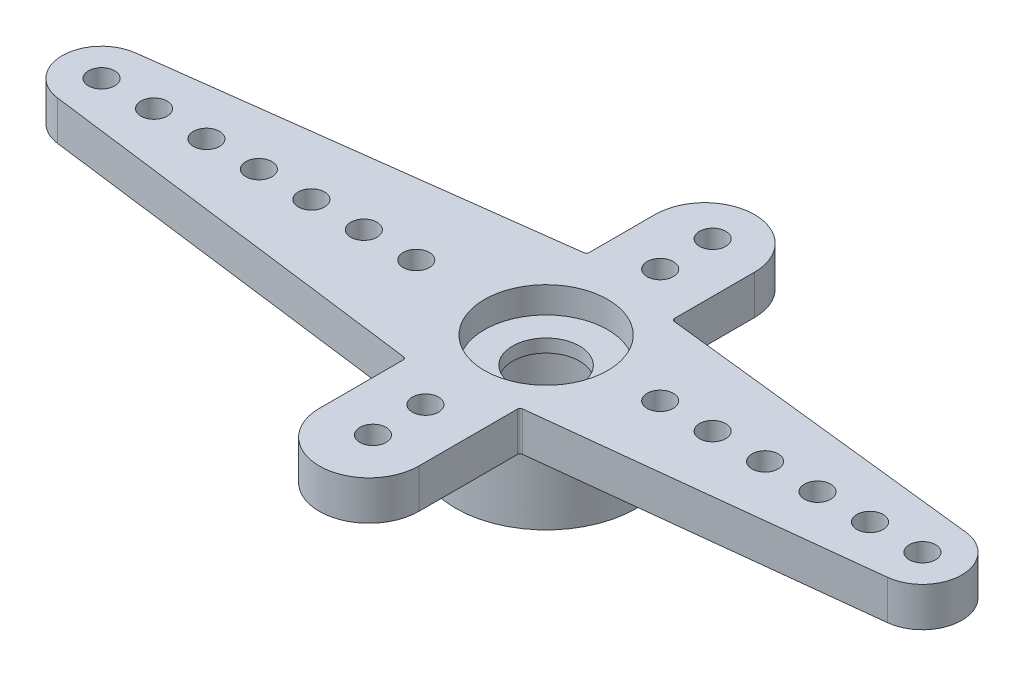
SolidWorks part; units mm, degrees
ref_plane "Ön Düzlem" through (0, 0, 0) normal (0, 0, 1) x (1, 0, 0)
ref_plane "Üst Düzlem" through (0, 0, 0) normal (0, 1, 0) x (1, 0, 0)
ref_plane "Sağ Düzlem" through (0, 0, 0) normal (1, 0, 0) x (0, 0, -1)
sketch "Çizim1" plane through (0, 0, 0) normal (0, 1, 0) x (1, 0, 0)
  line L0 (0, 11.8418) -> (0, -11.8418) construction
  line L1 (-16.95, 0) -> (14.35, 0) construction
  line L2 (-16.95, 0) -> (-14.95, 0) construction
  line L3 (14.35, 0) -> (12.35, 0) construction
  line L4 (-1.9, 6.05) -> (-1.9, 3.45)
  line L5 (1.9, -6.75) -> (1.9, -2.9)
  line L6 (-17.1415, 1.4877) -> (-1.9, 3.45)
  line L7 (-17.1415, -1.4877) -> (-1.9, -3.45)
  line L8 (14.5165, 1.4907) -> (1.9, 2.9)
  line L9 (14.5165, -1.4907) -> (1.9, -2.9)
  line L10 (1.9, 2.9) -> (1.9, 6.05)
  line L11 (-1.9, -3.45) -> (-1.9, -6.75)
  circle A0 centre (0, 0) radius 1.275
  circle A1 centre (0, 0) radius 2.35
  circle A2 centre (-16.95, 0) radius 0.5
  arc A3 (-17.1415, 1.4877) -> (-17.1415, -1.4877) centre (-16.95, 0) ccw
  circle A4 centre (-14.95, 0) radius 0.5
  circle A5 centre (-12.95, 0) radius 0.5
  circle A6 centre (-10.95, 0) radius 0.5
  circle A7 centre (-8.95, 0) radius 0.5
  circle A8 centre (-6.95, 0) radius 0.5
  circle A9 centre (-4.95, 0) radius 0.5
  circle A10 centre (14.35, 0) radius 0.5
  arc A11 (14.5165, -1.4907) -> (14.5165, 1.4907) centre (14.35, 0) ccw
  circle A12 centre (12.35, 0) radius 0.5
  circle A13 centre (10.35, 0) radius 0.5
  circle A14 centre (8.35, 0) radius 0.5
  circle A15 centre (6.35, 0) radius 0.5
  circle A16 centre (4.35, 0) radius 0.5
  circle A17 centre (0, 6.35) radius 0.5
  circle A18 centre (0, 4.35) radius 0.5
  circle A19 centre (0, -6.6) radius 0.5
  circle A20 centre (0, -4.6) radius 0.5
  arc A22 (-1.9, -6.75) -> (1.9, -6.75) centre (0, -6.75) ccw
  arc A23 (1.9, 6.05) -> (-1.9, 6.05) centre (0, 6.05) ccw
  point P5 (12.85, 0)
  point P6 (0, 0)
  point P10 (-17.45, 0)
  point P11 (-16.45, 0)
  point P14 (-2.35, 0)
  point P15 (2.35, 0)
  point P16 (15.85, 0)
  point P32 (13.85, 0)
  point P45 (3.85, 0)
  point P55 (0, 2.35)
  point P57 (-18.45, 0)
  point P62 (0, 7.95)
  point P63 (0, 6.85)
  point P64 (0, -7.1)
  point P65 (0, -8.65)
  point P66 (0, -2.35)
  dimension "D1" = 2.55
  dimension "D2" = 4.7
  dimension "D3" = 1
  dimension "D4" = 14.1
  dimension "D5" = 3
  dimension "D8" = 1
  dimension "D9" = 3
  dimension "D13" = 1
  dimension "D16" = 3.8
  dimension "D7" = 2
  dimension "D11" = 2
  dimension "D12" = 11.5
  dimension "D14" = 2
  dimension "D15" = 2
  dimension "D17" = 1.1
  dimension "D18" = 1.55
  dimension "D19" = 16.6
  dimension "D20" = 6.3
  dimension "D21" = 6.9
  dimension "D22" = 5.8
  dimension "D23" = 34.3
  dimension "D6" = 7
  dimension "D10" = 6
extrude "Yükseklik-Ekstrüzyon1" add sketch "Çizim1" along normal blind 1.5 contours L10 A23 L4 L6 A3 L7 L11 A22 L5 L9 A11 L8 A1 A2 A4 A5 A6 A7 A8 A9 A10 A12 A13 A14 A15 A16 A17 A18 A19 A20 region at (0, 0, -7.5689)
extrude "Yükseklik-Ekstrüzyon2" add sketch "Çizim1<3>" along normal blind 0.5 contours A1 A0 region at (-2.2835, 0, 0)
sketch "Çizim1<3>" plane through (0, 0, 0) normal (0, 1, 0) x (1, 0, 0) same geometry as "Çizim1"
sketch "Çizim2" plane through (0, 0, 0) normal (0, -1, 0) x (1, 0, 0)
  circle A0 centre (0, 0) radius 3.45
  circle A1 centre (0, 0) radius 2.3
  dimension "D1" = 6.9
  dimension "D2" = 1.15
extrude "Yükseklik-Ekstrüzyon3" add sketch "Çizim2" along normal blind 2.5
fillet "Radyus1" radius 0.1 4 edges at (-1.9, 0.75, -3.45) (1.9, 0.75, -2.9) (1.9, 0.75, 2.9) (-1.9, 0.75, 3.45)
